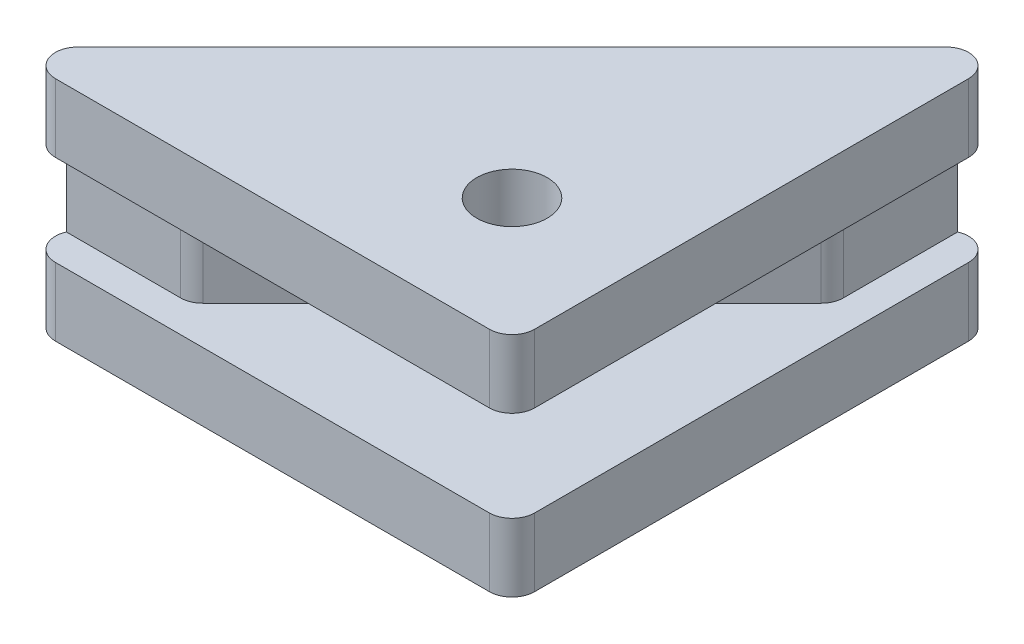
SolidWorks part; units mm, degrees
ref_plane "前视基准面" through (0, 0, 0) normal (0, 0, 1) x (1, 0, 0)
ref_plane "上视基准面" through (0, 0, 0) normal (0, 1, 0) x (1, 0, 0)
ref_plane "右视基准面" through (0, 0, 0) normal (1, 0, 0) x (0, 0, -1)
other "Configuration Table"
sketch "草图1" plane through (0, 0, 0) normal (0, 1, 0) x (1, 0, 0)
  line L0 (0, 0) -> (-45, 0)
  line L1 (0, 0) -> (0, 45)
  line L2 (0, 45) -> (-45, 0)
  dimension "D1" = 45
extrude "凸台-拉伸1" add sketch "草图1" along normal blind 6
sketch "草图2" plane through (0, 0, 0) normal (0, -1, 0) x (1, 0, 0)
  line L0 (-2.8, -42.2) -> (-2.8, -31.1411)
  line L1 (0, -45) -> (-45, 0) construction
  line L2 (-2.8, -31.1411) -> (-31.1411, -2.8)
  line L3 (-31.1411, -2.8) -> (-42.2, -2.8)
  line L4 (-42.2, -2.8) -> (-2.8, -42.2)
  point P6 (-3.8517, -25.9125)
  point P7 (-26.8744, -2.5618)
  dimension "D1" = 24
  dimension "D2" = 2.8
  dimension "D3" = 2.8
extrude "凸台-拉伸2" add sketch "草图2" along normal blind 8
extrude "凸台-拉伸3" add sketch "草图1<3>" against normal blind 6 from surface starting at face at (-19.7353, -8, -19.7353)
sketch "草图1<3>" plane through (0, 0, 0) normal (0, 1, 0) x (1, 0, 0) same geometry as "草图1"
sketch "草图3" plane through (0, -14, 0) normal (0, -1, 0) x (1, 0, 0)
  line L0 (0, 0) -> (-45, 0) construction
  line L1 (0, -45) -> (0, 0) construction
  circle A0 centre (-13, -13) radius 2.75
  dimension "D2" = 13
  dimension "D3" = 5.5
  dimension "D1" = 13
extrude "切除-拉伸1" cut sketch "草图3" against normal blind 8 and the other way through all
fillet "圆角1" radius 2 6 edges at (0, 3, 0) (0, -11, 0) (-31.1411, -4, -2.8) (-2.8, -4, -31.1411) (0, -11, -45) (-45, 3, 0)
sketch "草图4" plane through (0, 6, 0) normal (0, 1, 0) x (1, 0, 0)
  line L0 (0, 40.1716) -> (0, 2) construction
  line L1 (-2, 0) -> (-40.1716, 0) construction
  circle A0 centre (-11, 11) radius 3.1
  dimension "D1" = 6.2
  dimension "D2" = 11
  dimension "D3" = 11
extrude "切除-拉伸2" cut sketch "草图4" against normal blind 7
